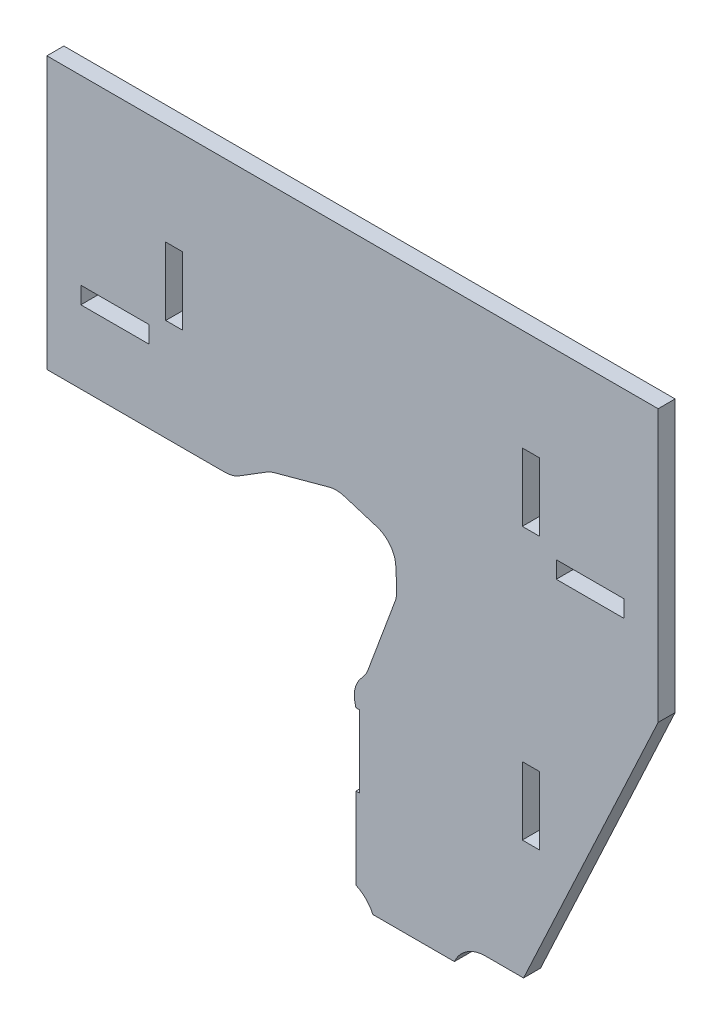
SolidWorks part; units mm, degrees
material "PBT General Purpose"
ref_plane "Front Plane" through (0, 0, 0) normal (0, 0, 1) x (1, 0, 0)
ref_plane "Top Plane" through (0, 0, 0) normal (0, 1, 0) x (1, 0, 0)
ref_plane "Right Plane" through (0, 0, 0) normal (1, 0, 0) x (0, 0, -1)
sketch "frame_outline" plane through (0, 0, 0) normal (0, 0, 1) x (1, 0, 0)
  line L0 (0, 0) -> (0, 0.3) construction
  line L1 (0, 0) -> (0.3, 0) construction
  line L2 (0, 0.3) -> (0.05, 0.3) construction
  line L3 (0.3, 0) -> (0.3, 0.05) construction
  line L4 (0.05, 0.3) -> (0.05, 1.5)
  line L5 (0.05, 1.5) -> (0.1, 1.5)
  line L6 (0.05, 0.3) -> (0.3, 0.3)
  line L7 (0.3, 0.3) -> (0.3, 0.05)
  line L8 (0.3, 0.05) -> (1.5, 0.05)
  line L9 (1.5, 0.05) -> (1.5, 0.35)
  line L10 (1.5, 0.35) -> (2.5182, 0.35)
  line L11 (2.5182, 0.35) -> (4.5, 4.6)
  line L12 (4.5, 4.6) -> (4.5, 8.6)
  line L13 (4.5, 8.6) -> (-4.5, 8.6)
  line L14 (-4.5, 8.6) -> (-4.5, 4.6)
  line L15 (-4.5, 4.6) -> (-1.7637, 4.6)
  line L16 (-1.7637, 4.6) -> (-1.2133, 4.9416)
  line L18 (0.1, 2.5625) -> (0.1, 1.5)
  line L19 (0, 8.6) -> (0, 0) construction
  line L20 (-2.5, 7.1) -> (2.5, 7.1) construction
  line L23 (-2.5, 7.1) -> (-2.75, 7.1)
  line L24 (-2.5, 7.1) -> (-2.5, 6.1)
  line L25 (-2.5, 6.1) -> (-2.75, 6.1)
  line L26 (-2.75, 7.1) -> (-2.75, 6.1)
  line L31 (2.5, 7.1) -> (2.75, 7.1)
  line L32 (2.5, 7.1) -> (2.5, 6.1)
  line L33 (2.5, 6.1) -> (2.75, 6.1)
  line L34 (2.75, 7.1) -> (2.75, 6.1)
  line L39 (2.5, 3.1) -> (2.75, 3.1)
  line L40 (2.5, 3.1) -> (2.5, 2.1)
  line L41 (2.5, 2.1) -> (2.75, 2.1)
  line L42 (2.75, 3.1) -> (2.75, 2.1)
  line L46 (-4, 5.925) -> (-3, 5.925)
  line L47 (-4, 5.925) -> (-4, 5.675)
  line L48 (-4, 5.675) -> (-3, 5.675)
  line L49 (-3, 5.925) -> (-3, 5.675)
  line L50 (3, 5.925) -> (4, 5.925)
  line L51 (3, 5.925) -> (3, 5.675)
  line L52 (3, 5.675) -> (4, 5.675)
  line L53 (4, 5.925) -> (4, 5.675)
  line L62 (-3, 5.8) -> (3, 5.8) construction
  line L63 (0.1, 2.5625) -> (0.05, 2.5625)
  line L64 (0.05, 2.5625) -> (-0.0089, 2.8119)
  line L65 (-0.0089, 2.8119) -> (0.2035, 3.0663)
  line L66 (0.2035, 3.0663) -> (0.655, 4.2832)
  line L67 (0.655, 4.2832) -> (0.6251, 4.9416)
  line L68 (0.6251, 4.9416) -> (-0.2329, 5.2084)
  line L69 (-0.2329, 5.2084) -> (-1.2133, 4.9416)
  point P26 (0, 7.3566)
  point P40 (0, 7.1)
  point P64 (0, 3.0425)
  point P65 (0, 5.8)
  point P87 (2.625, 2.1)
  dimension "D2" = 0.3
  dimension "D3" = 0.05
  dimension "D4" = 0.05
  dimension "D5" = 1.2
  dimension "D6" = 1.2
  dimension "D7" = 0.05
  dimension "D8" = 0.3
  dimension "D10" = 9
  dimension "D13" = 4
  dimension "D14" = 8.6
  dimension "D15" = 4
  dimension "D16" = 5
  dimension "D17" = 0.25
  dimension "D18" = 0.25
  dimension "D20" = 1
  dimension "D21" = 1
  dimension "D22" = 1.5
  dimension "D29" = 3
  dimension "D9" = 155
  dimension "D11" = 0.1068
  dimension "D12" = 3
  dimension "D19" = 0.25
  dimension "D23" = 1
  dimension "D24" = 2.8
extrude "Boss-Extrude1" add sketch "frame_outline" along normal mid plane 0.25
fillet "Fillet1" radius 0.5 2 edges at (1.5, 0.35, 0) (0.3, 0.3, 0)
fillet "Fillet2" radius 0.4 7 edges at (-1.7637, 4.6, 0) (-1.2133, 4.9416, 0) (-0.2329, 5.2084, 0) (0.6251, 4.9416, 0) (0.655, 4.2832, 0) (0.2035, 3.0663, 0) (-0.0089, 2.8119, 0)
equation "\"t\"= 0.25'thickness of the sheets"
equation "\"t_cf\" = 0.115'thickness of single carbon fiber layer"
equation "\"t_kapton\" = 0.025'thickness of single Kapton flex layer"
equation "\"t_fr4\" = 0.1'thickness of FR4 with copper layer"
equation "\"joint_flex\"= 0.1'Width of flextures gap"
equation "\"joint_flex_eff\"= 0.02'Width of flecture after castelation"
equation "\"joint_fold\"= 0.2'Width of folding joints for 90deg fold"
equation "\"gap_tolerance\"= 0.002'Width to have interfecence fit between carbon fiber inserts"
equation "\"assemble_angle\"= 90'Angle of assembly parts"
equation "\"D3@frame_outline\" = \"joint_flex\" / 2"
equation "\"D4@frame_outline\" = \"joint_flex\" / 2"
equation "\"D17@frame_outline\"=\"t\""
equation "\"D18@frame_outline\"=\"t\""
equation "\"D1@Boss-Extrude1\"=\"t\""
equation "\"link_lift\"= 0.5'Actuation linkage amplification for the lift motion"
equation "\"link_swing\"= 0.45'Actuation linkage amplification for the swing motion"
equation "\"D19@frame_outline\"=\"t\""
